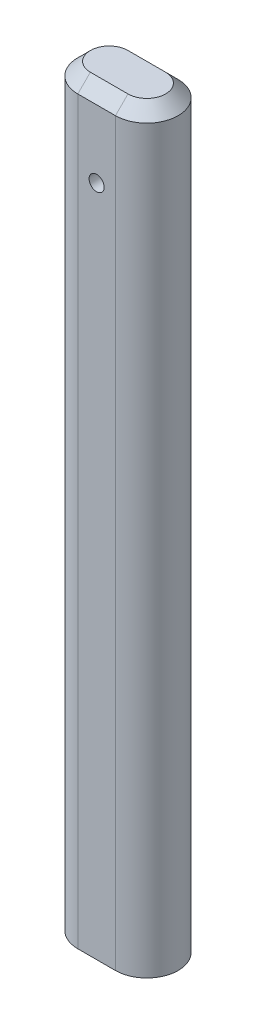
SolidWorks part; units mm, degrees
material "AISI 316 Annealed Stainless Steel Bar (SS)"
ref_plane "Front Plane" through (0, 0, 0) normal (0, 0, 1) x (1, 0, 0)
ref_plane "Top Plane" through (0, 0, 0) normal (0, 1, 0) x (1, 0, 0)
ref_plane "Right Plane" through (0, 0, 0) normal (1, 0, 0) x (0, 0, -1)
sketch "Sketch1" plane through (0, 0, 0) normal (0, 1, 0) x (1, 0, 0)
  line L0 (0, 0) -> (0, 25)
  line L1 (0, 0) -> (40, 0)
  line L2 (0, 25) -> (40, 25)
  line L3 (40, 25) -> (40, 0)
  dimension "D1" = 25
  dimension "D2" = 40
extrude "Boss-Extrude1" add sketch "Sketch1" along normal blind 300
fillet "Fillet1" 2 edges at (40, 150, 0) (40, 150, -25) type full round first side face at (20, 150, 0) second side face at (20, 150, -25) middle face at (40, 150, -12.5)
fillet "Fillet2" 2 edges at (0, 150, 0) (0, 150, -25) type full round first side face at (13.75, 150, 0) second side face at (13.75, 150, -25) middle face at (0, 150, -12.5)
chamfer "Chamfer1" distance 5 angle 45 4 edges at (20, 300, 0) (40, 300, -12.5) (0, 300, -12.5) (20, 300, -25)
sketch "Sketch2" plane through (0, 0, 0) normal (0, 0, 1) x (1, 0, 0)
  circle A0 centre (20, 32) radius 3
sketch "Sketch3" plane through (0, 0, 0) normal (0, 0, 1) x (1, 0, 0)
  circle A0 centre (20, 268) radius 3
extrude "Cut-Extrude2" cut sketch "Sketch3" against normal through all
